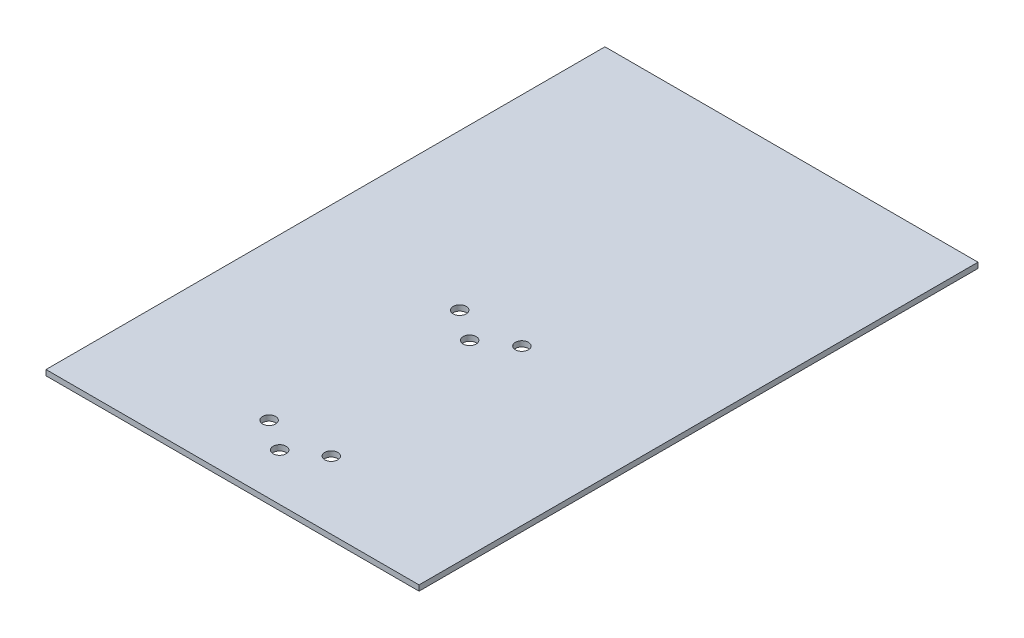
SolidWorks part; units mm, degrees
ref_plane "Front Plane" through (0, 0, 0) normal (0, 0, 1) x (1, 0, 0)
ref_plane "Top Plane" through (0, 0, 0) normal (0, 1, 0) x (1, 0, 0)
ref_plane "Right Plane" through (0, 0, 0) normal (1, 0, 0) x (0, 0, -1)
sketch "Sketch1" plane through (0, 0, 0) normal (0, 1, 0) x (1, 0, 0)
  line L1 (76.2, 0) -> (0, 0)
  line L2 (76.2, 0) -> (76.2, 114.173)
  line L3 (76.2, 114.173) -> (0, 114.173)
  line L4 (0, 0) -> (0, 114.173)
extrude "Boss-Extrude1" add sketch "Sketch1" along normal blind 1.1176
sketch "Sketch2" plane through (0, 1.1176, 0) normal (0, 1, 0) x (1, 0, 0)
  circle A0 centre (31.75, 13.8176) radius 1.3335
  circle A1 centre (44.45, 13.8176) radius 1.3335
  circle A2 centre (38.1, 9.6266) radius 1.3335
  circle A3 centre (31.75, 52.7558) radius 1.3335
  circle A4 centre (44.45, 52.7558) radius 1.3335
  circle A5 centre (38.1, 48.4378) radius 1.3335
extrude "Cut-Extrude1" cut sketch "Sketch2" against normal blind 2.54
